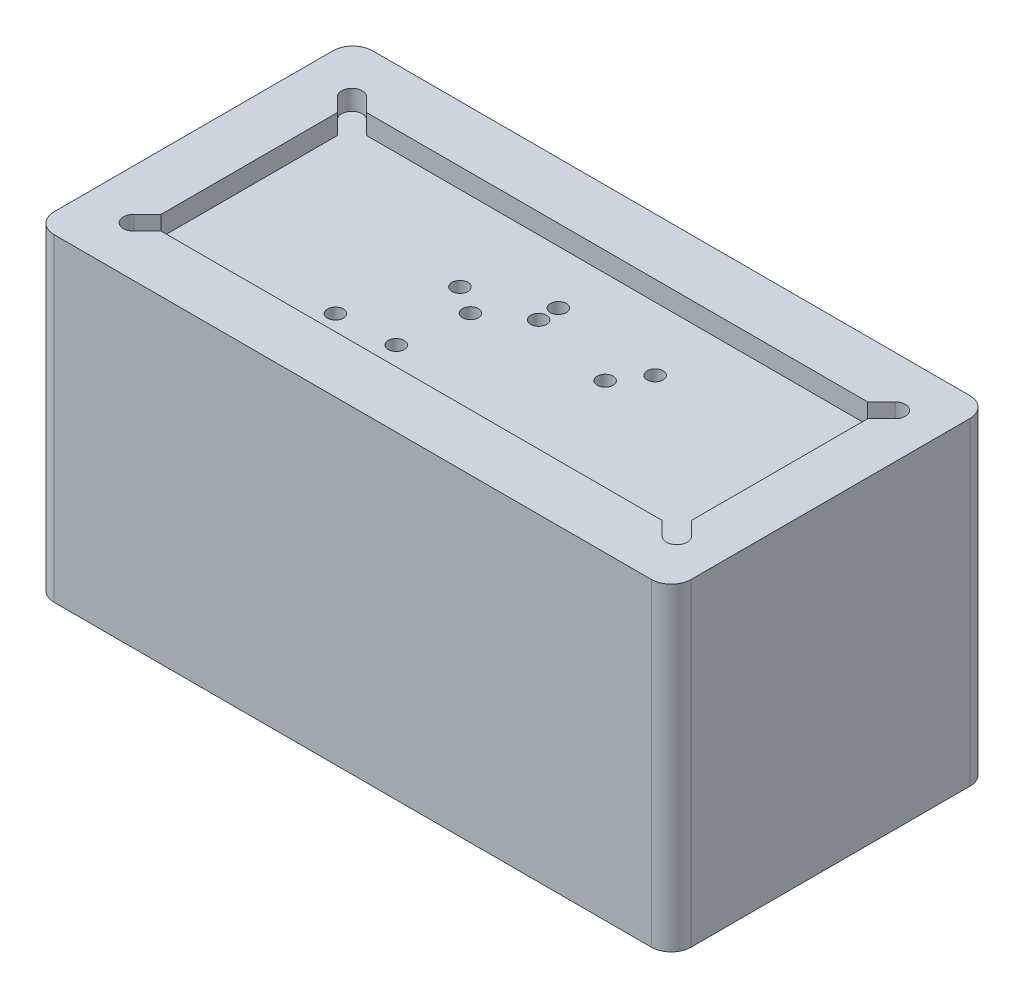
SolidWorks part; units mm, degrees
ref_plane "Front" through (0, 0, 0) normal (0, 0, 1) x (1, 0, 0)
ref_plane "Top" through (0, 0, 0) normal (0, 1, 0) x (1, 0, 0)
ref_plane "Right" through (0, 0, 0) normal (1, 0, 0) x (0, 0, -1)
sketch "Sketch1" plane through (0, 0, 0) normal (0, 1, 0) x (1, 0, 0)
  line L0 (-25.4, -12.7) -> (25.4, 12.7) construction
  line L1 (-25.4, 12.7) -> (25.4, 12.7)
  line L2 (-25.4, 12.7) -> (-25.4, -12.7)
  line L3 (-25.4, -12.7) -> (25.4, -12.7)
  line L4 (25.4, 12.7) -> (25.4, -12.7)
  point P4 (0, 0)
  dimension "D1" = 25.4
  dimension "D2" = 50.8
extrude "Boss-Extrude1" add sketch "Sketch1" along normal blind 25.4
sketch "Sketch5" plane through (0, 0, 0) normal (0, -1, 0) x (1, 0, 0)
  line L0 (-20.828, -7.9375) -> (21.082, -7.9375)
  line L1 (21.082, -7.9375) -> (21.082, 7.9375)
  line L2 (21.082, 7.9375) -> (-20.828, 7.9375)
  line L3 (-20.828, 7.9375) -> (-20.828, -7.9375)
  line L4 (-0.4953, -4.7238) -> (-0.4953, -5.461)
  line L5 (-0.4953, -5.461) -> (-0.1267, -5.461)
  line L6 (-0.1267, -5.461) -> (-0.0038, -5.3381)
  line L7 (-0.0038, -5.3381) -> (-0.0038, -4.8467)
  line L8 (-0.0038, -4.8467) -> (-0.1267, -4.7238)
  line L9 (-0.1267, -4.7238) -> (-0.4953, -4.7238)
  line L10 (-3.6868, 6.1007) -> (-3.8097, 6.2236)
  line L11 (-3.8097, 6.2236) -> (-4.0554, 6.2236)
  line L12 (-4.0554, 6.2236) -> (-4.1783, 6.1007)
  line L13 (-4.1783, 6.1007) -> (-4.1783, 5.6093)
  line L14 (-4.1783, 5.6093) -> (-4.0554, 5.4864)
  line L15 (-4.0554, 5.4864) -> (-3.8097, 5.4864)
  line L16 (-3.8097, 5.4864) -> (-3.6868, 5.6093)
  line L17 (-9.5034, 6.6849) -> (-9.6263, 6.8078)
  line L18 (-9.6263, 6.8078) -> (-9.872, 6.8078)
  line L19 (-9.872, 6.8078) -> (-9.9949, 6.6849)
  line L20 (-9.9949, 6.6849) -> (-9.9949, 6.1935)
  line L21 (-9.9949, 6.1935) -> (-9.872, 6.0706)
  line L22 (-9.872, 6.0706) -> (-9.6263, 6.0706)
  line L23 (-9.6263, 6.0706) -> (-9.5034, 6.1935)
  line L24 (-9.5034, 6.1935) -> (-9.5034, 6.4392)
  line L25 (-9.5034, 6.4392) -> (-9.7492, 6.4392)
  line L26 (0.1651, -2.5908) -> (0.1651, -1.8536)
  line L27 (0.1651, -1.8536) -> (0.5337, -1.8536)
  line L28 (0.5337, -1.8536) -> (0.6566, -1.9765)
  line L29 (0.6566, -1.9765) -> (0.6566, -2.2222)
  line L30 (0.6566, -2.2222) -> (0.5337, -2.3451)
  line L31 (0.5337, -2.3451) -> (0.1651, -2.3451)
  line L32 (0.4108, -2.3451) -> (0.6566, -2.5908)
  line L33 (-5.4483, 0.2546) -> (-5.4483, -0.2369)
  line L34 (-5.4483, -0.2369) -> (-5.2026, -0.4826)
  line L35 (-5.2026, -0.4826) -> (-4.9568, -0.2369)
  line L36 (-4.9568, -0.2369) -> (-4.9568, 0.2546)
  line L37 (-4.6863, -0.4826) -> (-4.6863, 0.2546)
  line L38 (-4.6863, 0.2546) -> (-4.4406, 0.0089)
  line L39 (-4.4406, 0.0089) -> (-4.1948, 0.2546)
  line L40 (-4.1948, 0.2546) -> (-4.1948, -0.4826)
  arc A0 (21.082, -7.9375) -> (21.082, -7.9311) centre (21.082, -7.9343) ccw
  arc A1 (-20.828, -7.9375) -> (-20.828, -7.9438) centre (-20.828, -7.9407) ccw
  arc A2 (21.082, 7.9375) -> (21.0757, 7.9375) centre (21.0788, 7.9375) ccw
  arc A3 (21.082, -7.9375) -> (21.0883, -7.9375) centre (21.0852, -7.9375) ccw
  arc A4 (-20.828, 7.9375) -> (-20.828, 7.9311) centre (-20.828, 7.9343) ccw
  arc A5 (21.082, 7.9375) -> (21.082, 7.9438) centre (21.082, 7.9407) ccw
  arc A6 (-20.828, -7.9375) -> (-20.8216, -7.9375) centre (-20.8248, -7.9375) ccw
  arc A7 (-20.828, 7.9375) -> (-20.8343, 7.9375) centre (-20.8312, 7.9375) ccw
  arc A8 (-0.4953, -5.461) -> (-0.4762, -5.461) centre (-0.4858, -5.461) ccw
  arc A9 (-0.4953, -4.7238) -> (-0.5143, -4.7238) centre (-0.5048, -4.7238) ccw
  arc A10 (-0.1132, -5.4745) -> (-0.1267, -5.442) centre (-0.12, -5.4582) ccw
  arc A11 (-0.4953, -5.461) -> (-0.4953, -5.48) centre (-0.4953, -5.4705) ccw
  arc A12 (0.0152, -5.3381) -> (-0.0173, -5.3247) centre (-0.001, -5.3314) ccw
  arc A13 (-0.1267, -5.442) -> (-0.1132, -5.4745) centre (-0.12, -5.4582) ccw
  arc A14 (0.0097, -4.8332) -> (-0.0229, -4.8467) centre (-0.0066, -4.8399) ccw
  arc A15 (-0.0173, -5.3247) -> (0.0152, -5.3381) centre (-0.001, -5.3314) ccw
  arc A16 (-0.1267, -4.7047) -> (-0.1402, -4.7373) centre (-0.1334, -4.721) ccw
  arc A17 (-0.0229, -4.8467) -> (0.0097, -4.8332) centre (-0.0066, -4.8399) ccw
  arc A18 (-0.4953, -4.7238) -> (-0.4953, -4.7428) centre (-0.4953, -4.7333) ccw
  arc A19 (-0.1402, -4.7373) -> (-0.1267, -4.7047) centre (-0.1334, -4.721) ccw
  arc A20 (-3.8097, 6.2427) -> (-3.8232, 6.2101) centre (-3.8164, 6.2264) ccw
  arc A21 (-3.6868, 6.1007) -> (-3.6733, 6.1142) centre (-3.6801, 6.1075) ccw
  arc A22 (-4.0689, 6.2371) -> (-4.0554, 6.2046) centre (-4.0622, 6.2208) ccw
  arc A23 (-3.8232, 6.2101) -> (-3.8097, 6.2427) centre (-3.8164, 6.2264) ccw
  arc A24 (-4.1973, 6.1007) -> (-4.1648, 6.0873) centre (-4.1811, 6.094) ccw
  arc A25 (-4.0554, 6.2046) -> (-4.0689, 6.2371) centre (-4.0622, 6.2208) ccw
  arc A26 (-4.1918, 5.5958) -> (-4.1592, 5.6093) centre (-4.1755, 5.6025) ccw
  arc A27 (-4.1648, 6.0873) -> (-4.1973, 6.1007) centre (-4.1811, 6.094) ccw
  arc A28 (-4.0554, 5.4674) -> (-4.042, 5.4999) centre (-4.0487, 5.4836) ccw
  arc A29 (-4.1592, 5.6093) -> (-4.1918, 5.5958) centre (-4.1755, 5.6025) ccw
  arc A30 (-3.7962, 5.4729) -> (-3.8097, 5.5054) centre (-3.803, 5.4892) ccw
  arc A31 (-4.042, 5.4999) -> (-4.0554, 5.4674) centre (-4.0487, 5.4836) ccw
  arc A32 (-3.6868, 5.6093) -> (-3.7003, 5.6227) centre (-3.6936, 5.616) ccw
  arc A33 (-3.8097, 5.5054) -> (-3.7962, 5.4729) centre (-3.803, 5.4892) ccw
  arc A34 (-9.6263, 6.8269) -> (-9.6398, 6.7943) centre (-9.633, 6.8106) ccw
  arc A35 (-9.5034, 6.6849) -> (-9.4899, 6.6984) centre (-9.4967, 6.6917) ccw
  arc A36 (-9.8855, 6.8213) -> (-9.872, 6.7888) centre (-9.8788, 6.805) ccw
  arc A37 (-9.6398, 6.7943) -> (-9.6263, 6.8269) centre (-9.633, 6.8106) ccw
  arc A38 (-10.0139, 6.6849) -> (-9.9814, 6.6715) centre (-9.9977, 6.6782) ccw
  arc A39 (-9.872, 6.7888) -> (-9.8855, 6.8213) centre (-9.8788, 6.805) ccw
  arc A40 (-10.0084, 6.18) -> (-9.9758, 6.1935) centre (-9.9921, 6.1867) ccw
  arc A41 (-9.9814, 6.6715) -> (-10.0139, 6.6849) centre (-9.9977, 6.6782) ccw
  arc A42 (-9.872, 6.0515) -> (-9.8586, 6.0841) centre (-9.8653, 6.0678) ccw
  arc A43 (-9.9758, 6.1935) -> (-10.0084, 6.18) centre (-9.9921, 6.1867) ccw
  arc A44 (-9.6128, 6.0571) -> (-9.6263, 6.0897) centre (-9.6196, 6.0734) ccw
  arc A45 (-9.8586, 6.0841) -> (-9.872, 6.0515) centre (-9.8653, 6.0678) ccw
  arc A46 (-9.4844, 6.1935) -> (-9.5169, 6.2069) centre (-9.5006, 6.2002) ccw
  arc A47 (-9.6263, 6.0897) -> (-9.6128, 6.0571) centre (-9.6196, 6.0734) ccw
  arc A48 (-9.5034, 6.4392) -> (-9.5225, 6.4392) centre (-9.5129, 6.4392) ccw
  arc A49 (-9.5169, 6.2069) -> (-9.4844, 6.1935) centre (-9.5006, 6.2002) ccw
  arc A50 (-9.7492, 6.4392) -> (-9.7492, 6.4202) centre (-9.7492, 6.4297) ccw
  arc A51 (-9.5034, 6.4392) -> (-9.5034, 6.4583) centre (-9.5034, 6.4487) ccw
  arc A52 (0.1651, -1.8536) -> (0.1461, -1.8536) centre (0.1556, -1.8536) ccw
  arc A53 (0.1651, -2.5908) -> (0.1842, -2.5908) centre (0.1746, -2.5908) ccw
  arc A54 (0.5202, -1.8671) -> (0.5337, -1.8345) centre (0.527, -1.8508) ccw
  arc A55 (0.1651, -1.8536) -> (0.1651, -1.8726) centre (0.1651, -1.8631) ccw
  arc A56 (0.6375, -1.9765) -> (0.6701, -1.963) centre (0.6538, -1.9697) ccw
  arc A57 (0.5337, -1.8345) -> (0.5202, -1.8671) centre (0.527, -1.8508) ccw
  arc A58 (0.6431, -2.2087) -> (0.6756, -2.2222) centre (0.6594, -2.2155) ccw
  arc A59 (0.6701, -1.963) -> (0.6375, -1.9765) centre (0.6538, -1.9697) ccw
  arc A60 (0.5337, -2.326) -> (0.5472, -2.3585) centre (0.5404, -2.3423) ccw
  arc A61 (0.6756, -2.2222) -> (0.6431, -2.2087) centre (0.6594, -2.2155) ccw
  arc A62 (0.1651, -2.3451) -> (0.1651, -2.3641) centre (0.1651, -2.3546) ccw
  arc A63 (0.5472, -2.3585) -> (0.5337, -2.326) centre (0.5404, -2.3423) ccw
  arc A64 (0.6566, -2.5908) -> (0.6701, -2.5773) centre (0.6633, -2.5841) ccw
  arc A65 (0.4108, -2.3451) -> (0.3974, -2.3585) centre (0.4041, -2.3518) ccw
  arc A66 (-5.4618, -0.2503) -> (-5.4292, -0.2369) centre (-5.4455, -0.2436) ccw
  arc A67 (-5.4483, 0.2546) -> (-5.4673, 0.2546) centre (-5.4578, 0.2546) ccw
  arc A68 (-5.2026, -0.4826) -> (-5.1891, -0.4691) centre (-5.1958, -0.4759) ccw
  arc A69 (-5.4292, -0.2369) -> (-5.4618, -0.2503) centre (-5.4455, -0.2436) ccw
  arc A70 (-4.9378, -0.2369) -> (-4.9703, -0.2234) centre (-4.954, -0.2301) ccw
  arc A71 (-5.2026, -0.4826) -> (-5.1891, -0.4961) centre (-5.1958, -0.4893) ccw
  arc A72 (-4.9568, 0.2546) -> (-4.9759, 0.2546) centre (-4.9663, 0.2546) ccw
  arc A73 (-4.9703, -0.2234) -> (-4.9378, -0.2369) centre (-4.954, -0.2301) ccw
  arc A74 (-4.6672, 0.2546) -> (-4.7053, 0.2546) centre (-4.6863, 0.2546) ccw
  arc A75 (-4.6863, -0.4826) -> (-4.6672, -0.4826) centre (-4.6768, -0.4826) ccw
  arc A76 (-4.4406, 0.0089) -> (-4.4271, 0.0224) centre (-4.4338, 0.0156) ccw
  arc A77 (-4.6672, 0.2546) -> (-4.6998, 0.2411) centre (-4.6835, 0.2479) ccw
  arc A78 (-4.1813, 0.2411) -> (-4.2083, 0.2681) centre (-4.1948, 0.2546) ccw
  arc A79 (-4.4406, 0.0089) -> (-4.4271, -0.0046) centre (-4.4338, 0.0021) ccw
  arc A80 (-4.1948, -0.4826) -> (-4.1758, -0.4826) centre (-4.1853, -0.4826) ccw
  arc A81 (-4.1813, 0.2411) -> (-4.2139, 0.2546) centre (-4.1976, 0.2479) ccw
  circle A82 centre (-5.6134, -1.4605) radius 0.3175
  arc A118 (-3.7748, 6.1722) -> (-3.7748, 6.1913) centre (-3.7748, 6.1817) ccw
  circle A267 centre (-8.7376, 5.3467) radius 0.3175
  circle A276 centre (-3.3782, -0.0635) radius 0.3175
  circle A277 centre (6.6548, -0.7747) radius 0.3175
  circle A278 centre (8.2804, -3.1369) radius 0.3175
  circle A599 centre (-0.2032, -2.3241) radius 0.3175
  circle A600 centre (-4.1402, 5.0927) radius 0.3175
  circle A601 centre (-0.2286, -3.9243) radius 0.3175
sketch "Sketch6" plane through (0, 25.4, 0) normal (0, 1, 0) x (1, 0, 0)
  circle A0 centre (-5.6134, 1.4605) radius 0.635
  circle A1 centre (-0.2286, 3.9243) radius 0.635
  circle A2 centre (-0.2032, 2.3241) radius 0.635
  circle A3 centre (-4.1402, -5.0927) radius 0.635
  circle A4 centre (-8.7376, -5.3467) radius 0.635
  circle A5 centre (6.6548, 0.7747) radius 0.635
  circle A6 centre (8.2804, 3.1369) radius 0.635
  circle A7 centre (-3.3782, 0.0635) radius 0.635
  dimension "D1" = 1.27
extrude "Cut-Extrude1" cut sketch "Sketch6" against normal through all
sketch "Sketch7" plane through (0, 25.4, 0) normal (0, 1, 0) x (1, 0, 0)
  line L0 (-20.828, 7.9375) -> (21.082, 7.9375) construction
  line L1 (-20.828, -7.9375) -> (-20.828, 7.9375) construction
  line L2 (21.082, -7.9375) -> (-20.828, -7.9375) construction
  line L3 (21.082, 7.9375) -> (21.082, -7.9375) construction
  line L4 (-20.828, 7.9375) -> (21.082, 7.9375) construction
  line L5 (-20.828, -7.9375) -> (-20.828, 7.9375) construction
  line L6 (21.082, -7.9375) -> (-20.828, -7.9375) construction
  line L7 (21.082, 7.9375) -> (21.082, -7.9375) construction
  line L8 (-20.955, -7.0241) -> (-20.955, 7.0241)
  line L9 (-19.7876, 8.1915) -> (20.1686, 8.1915)
  line L12 (-22.0467, -8.1158) -> (-20.955, -7.0241)
  line L13 (-20.8793, -9.2832) -> (-19.7876, -8.1915)
  line L14 (21.2603, -9.2832) -> (20.1686, -8.1915)
  line L15 (22.4277, -8.1158) -> (21.336, -7.0241)
  line L16 (21.2603, 9.2832) -> (20.1686, 8.1915)
  line L17 (22.4277, 8.1158) -> (21.336, 7.0241)
  line L18 (-22.0467, 8.1158) -> (-20.955, 7.0241)
  line L19 (-20.8793, 9.2832) -> (-19.7876, 8.1915)
  line L20 (20.1686, -8.1915) -> (-19.7876, -8.1915)
  line L21 (21.336, 7.0241) -> (21.336, -7.0241)
  arc A0 (-20.8793, 9.2832) -> (-22.0467, 8.1158) centre (-21.463, 8.6995) ccw
  arc A1 (22.4277, 8.1158) -> (21.2603, 9.2832) centre (21.844, 8.6995) ccw
  arc A3 (21.2603, -9.2832) -> (22.4277, -8.1158) centre (21.844, -8.6995) ccw
  arc A4 (-22.0467, -8.1158) -> (-20.8793, -9.2832) centre (-21.463, -8.6995) ccw
  point P4 (-21.082, 8.1915)
  point P5 (21.336, 8.1915)
  point P6 (21.336, -8.1915)
  point P7 (-21.082, -8.1915)
  dimension "D2" = 0.508
  dimension "D6" = 1.651
  dimension "D3" = 0.508
  dimension "D4" = 0.254
  dimension "D5" = 0.254
  dimension "D7" = 0.254
  dimension "D1" = 0.508
  dimension "D8" = 0.254
  dimension "D9" = 0.508
extrude "Cut-Extrude2" cut sketch "Sketch7" against normal blind 1.5875
sketch "Sketch8" plane through (0, 0, 0) normal (0, -1, 0) x (1, 0, 0)
  line L4 (22.86, 10.16) -> (-22.86, 10.16)
  line L5 (-22.86, 10.16) -> (-22.86, 3.175)
  line L6 (-22.86, -10.16) -> (22.86, -10.16)
  line L7 (22.86, -10.16) -> (22.86, 10.16)
  line L8 (-25.4, -12.7) -> (-25.4, 12.7) construction
  line L9 (-25.4, -3.175) -> (-25.4, 3.175)
  line L10 (-25.4, 3.175) -> (-22.86, 3.175)
  line L11 (-22.86, -3.175) -> (-25.4, -3.175)
  line L12 (-22.86, -3.175) -> (-22.86, -10.16)
  line L13 (-25.4, 12.7) -> (25.4, 12.7) construction
  line L14 (25.4, 12.7) -> (25.4, -12.7) construction
  line L15 (25.4, -12.7) -> (-25.4, -12.7) construction
  dimension "D1" = 6.35
  dimension "D2" = 3.175
  dimension "D3" = 2.54
  dimension "D4" = 2.54
  dimension "D5" = 2.54
  dimension "D6" = 2.54
extrude "Cut-Extrude3" cut sketch "Sketch8" against normal blind 3.175
fillet "Fillet1" radius 3.302 4 edges at (-22.86, 1.5875, -10.16) (22.86, 1.5875, -10.16) (22.86, 1.5875, 10.16) (-22.86, 1.5875, 10.16)
fillet "Fillet2" radius 0.8128 2 edges at (-22.86, 1.5875, -3.175) (-22.86, 1.5875, 3.175)
chamfer "Chamfer1" distance 0.635 angle 45 8 edges at (8.2804, 3.175, -3.7719) (6.6548, 3.175, -1.4097) (-0.2286, 3.175, -4.5593) (-0.2032, 3.175, -2.9591) (-5.6134, 3.175, -2.0955) (-3.3782, 3.175, -0.6985) (-4.1402, 3.175, 4.4577) (-8.7376, 3.175, 4.7117)
fillet "Fillet3" radius 1.5875 4 edges at (25.4, 12.7, -12.7) (25.4, 12.7, 12.7) (-25.4, 12.7, -12.7) (-25.4, 12.7, 12.7)
